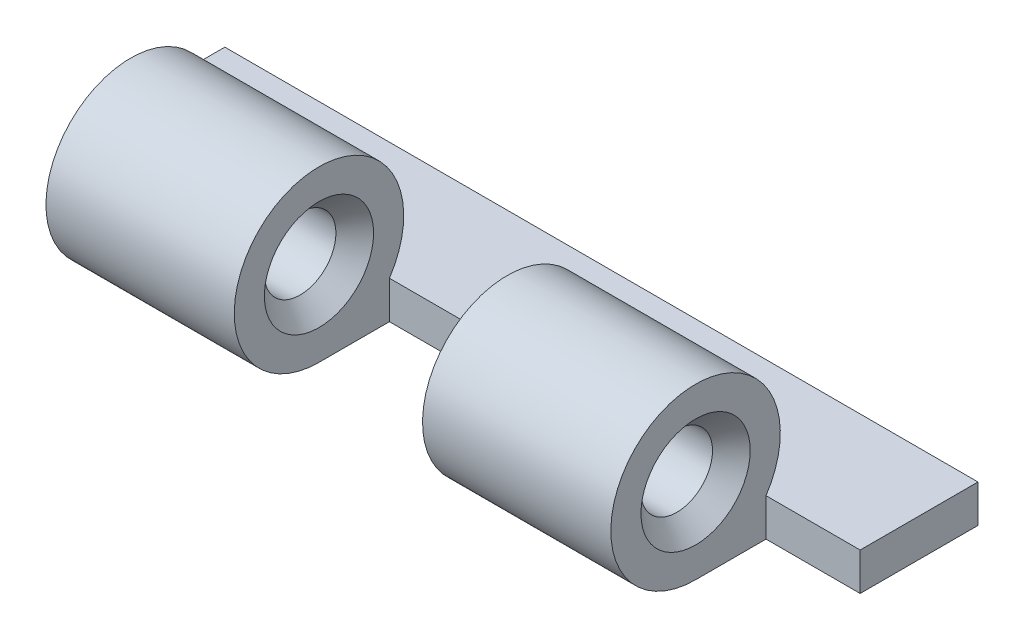
SolidWorks part; units mm, degrees
ref_plane "Ebene vorne" through (0, 0, 0) normal (0, 0, 1) x (1, 0, 0)
ref_plane "Ebene oben" through (0, 0, 0) normal (0, 1, 0) x (1, 0, 0)
ref_plane "Ebene rechts" through (0, 0, 0) normal (1, 0, 0) x (0, 0, -1)
sketch "Skizze2" plane through (0, 0, 0) normal (0, 1, 0) x (1, 0, 0)
  line L1 (-7.5, 2.5) -> (7.5, 2.5)
  line L2 (-7.5, 2.5) -> (-7.5, -2.5)
  line L3 (-7.5, -2.5) -> (7.5, -2.5)
  line L4 (7.5, 2.5) -> (7.5, -2.5)
  line L5 (-7.5, 2.5) -> (7.5, -2.5) construction
  line L6 (-7.5, -2.5) -> (7.5, 2.5) construction
  point P0 (0, 0)
  dimension "D1" = 15
  dimension "D2" = 5
extrude "Aufsatz-Linear austragen1" add sketch "Skizze2" along normal blind 1
sketch "Skizze3" plane through (7.5, 0, 0) normal (1, 0, 0) x (0, 0, -1)
  circle A0 centre (-2.5, 2.25) radius 2.25
  circle A1 centre (-2.5, 2.25) radius 0.95
  dimension "D1" = 1.9
  dimension "D2" = 4.5
extrude "Aufsatz-Linear austragen2" add sketch "Skizze3" against normal up to surface (15 mm away) up to face at (-7.5, 0.5, 0)
ref_plane "Tangential Ebene" through (0, 0, 0.25) normal (0, 0, -1) x (-1, 0, 0)
sketch "Skizze5" plane through (7.5, 0, 0) normal (1, 0, 0) x (0, 0, -1)
  line L0 (-0.6292, 1) -> (-0.6292, 0)
  line L1 (-0.6292, 0) -> (-2.5, 0)
  line L3 (2.5, 1) -> (-0.6292, 1)
  line L4 (-2.5, 0) -> (2.5, 0)
  line L5 (2.5, 0) -> (2.5, 1)
  line L6 (2.5, 1) -> (-0.6292, 1) construction
  line L7 (-2.5, 0) -> (2.5, 0) construction
  line L8 (2.5, 0) -> (2.5, 1) construction
  arc A1 (-0.6292, 1) -> (-2.5, 0) centre (-2.5, 2.25) ccw
  arc A2 (-0.6292, 1) -> (-2.5, 0) centre (-2.5, 2.25) ccw
  dimension "D1" = 0
extrude "Schnitt-Linear austragen1" cut sketch "Skizze5" against normal blind 5 from offset 5 offset against normal yes
ref_plane "Spiegelebene" through (0, 0, 0) normal (1, 0, 0) x (0, 0, -1)
sketch "Skizze7" plane through (7.5, 0, 0) normal (1, 0, 0) x (0, 0, -1)
  line L1 (-0.6292, 1) -> (2.5, 1)
  line L2 (-0.6292, 1) -> (-0.6292, 0)
  line L3 (-0.6292, 0) -> (2.5, 0)
  line L4 (2.5, 1) -> (2.5, 0)
extrude "Aufsatz-Linear austragen3" add sketch "Skizze7" along normal blind 2.5
mirror "Spiegeln1" about plane through (0, 0, 0) normal (1, 0, 0) of "Aufsatz-Linear austragen3"
chamfer "Fase1" distance 0.5 angle 45 4 edges at (-7.5, 2.25, 1.55) (-2.5, 2.25, 1.55) (2.5, 2.25, 1.55) (7.5, 2.25, 1.55)
